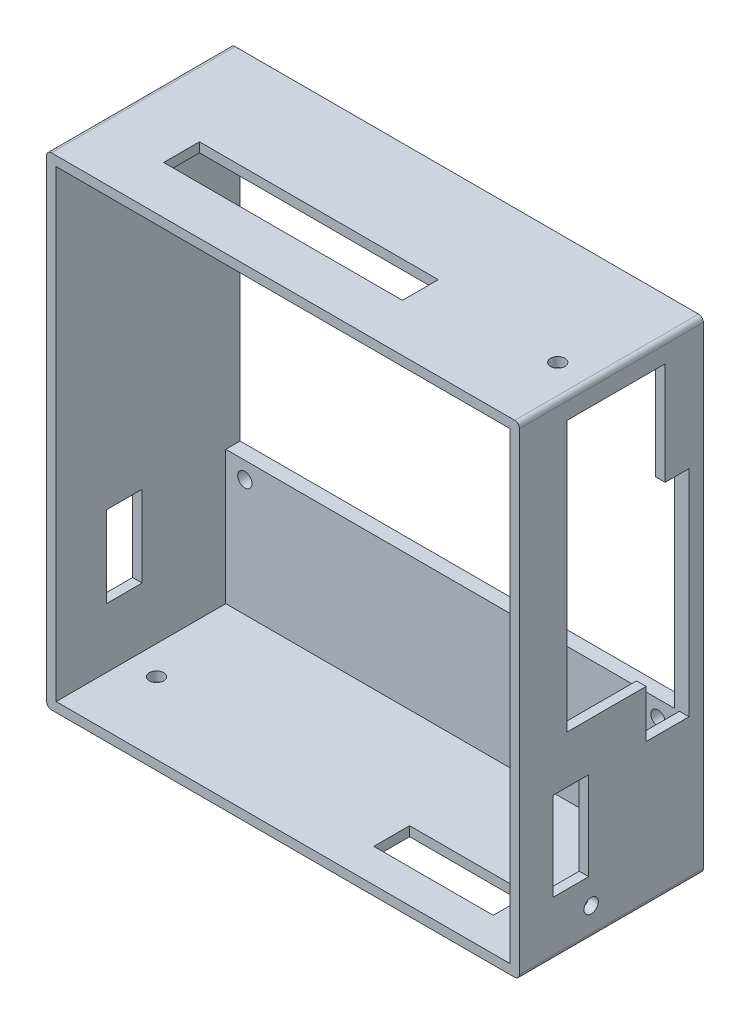
SolidWorks part; units mm, degrees
ref_plane "前视基准面" through (0, 0, 0) normal (0, 0, 1) x (1, 0, 0)
ref_plane "上视基准面" through (0, 0, 0) normal (0, 1, 0) x (1, 0, 0)
ref_plane "右视基准面" through (0, 0, 0) normal (1, 0, 0) x (0, 0, -1)
sketch "草图1" plane through (0, 0, 0) normal (0, 0, 1) x (1, 0, 0)
  line L1 (-47.5, -30.5) -> (47.5, -30.5)
  line L2 (-47.5, -30.5) -> (-47.5, 30.5)
  line L3 (-47.5, 30.5) -> (47.5, 30.5)
  line L4 (47.5, -30.5) -> (47.5, 30.5)
  line L5 (-47.5, -30.5) -> (47.5, 30.5) construction
  line L6 (-47.5, 30.5) -> (47.5, -30.5) construction
  line L10 (-49.5, 40.5) -> (49.5, 40.5)
  line L11 (49.5, 40.5) -> (49.5, -63.5)
  line L12 (49.5, -63.5) -> (-49.5, -63.5)
  line L13 (-49.5, -63.5) -> (-49.5, 40.5)
  circle A0 centre (43, 34) radius 1.5
  circle A1 centre (-43.5, 34) radius 1.5
  circle A2 centre (-43.5, -34) radius 1.5
  circle A3 centre (43, -34) radius 1.5
  point P0 (0, 0)
extrude "凸台-拉伸3" add sketch "草图1" along normal blind 3
sketch "草图3" plane through (0, 0, 3) normal (0, 0, 1) x (1, 0, 0)
  line L0 (-47.5, 38.5) -> (-47.5, -61.5)
  line L1 (-47.5, -61.5) -> (47.5, -61.5)
  line L2 (47.5, -61.5) -> (47.5, 38.5)
  line L3 (47.5, 38.5) -> (-47.5, 38.5)
  line L4 (-49.5, 40.5) -> (-49.5, -63.5)
  line L5 (-49.5, -63.5) -> (49.5, -63.5)
  line L6 (49.5, -63.5) -> (49.5, 40.5)
  line L7 (49.5, 40.5) -> (-49.5, 40.5)
  line L8 (-49.5, 40.5) -> (-49.5, -63.5)
  line L9 (-49.5, -63.5) -> (49.5, -63.5)
  line L10 (49.5, -63.5) -> (49.5, 40.5)
  line L11 (49.5, 40.5) -> (-49.5, 40.5)
  dimension "D1" = 0
  dimension "D2" = 2
extrude "凸台-拉伸4" add sketch "草图3" along normal blind 33
sketch "草图4" plane through (47.5, 0, 0) normal (-1, 0, 0) x (0, 0, 1)
  line L2 (12, 14.5) -> (12, -30.5)
  line L3 (12, -30.5) -> (3, -30.5)
  line L5 (0, 14.5) -> (0, -30.5)
  line L6 (0, -30.5) -> (3, -30.5)
  line L7 (12, 14.5) -> (0, 14.5)
extrude "切除-拉伸2" cut sketch "草图4" against normal blind 30
sketch "草图5" plane through (0, 40.5, 0) normal (0, 1, 0) x (1, 0, 0)
  line L0 (15, -28.5) -> (-35, -28.5)
  line L2 (-35, -21) -> (15, -21)
  line L3 (-35, -28.5) -> (-35, -21)
  line L4 (15, -21) -> (15, -28.5)
extrude "切除-拉伸3" cut sketch "草图5" against normal blind 30
sketch "草图6" plane through (47.5, 0, 0) normal (-1, 0, 0) x (0, 0, 1)
  line L0 (36, 38.5) -> (36, -16.5)
  line L1 (36, -61.5) -> (36, 38.5) construction
  line L2 (36, 38.5) -> (3, 38.5) construction
  line L3 (36, -16.5) -> (8, -16.5)
  line L4 (8, -16.5) -> (8, 38.5)
  line L5 (8, 38.5) -> (36, 38.5)
extrude "切除-拉伸4" cut sketch "草图6" against normal blind 30
sketch "草图7" plane through (47.5, 0, 0) normal (-1, 0, 0) x (0, 0, 1)
  line L1 (24, -30.5) -> (24, -49)
  line L5 (24, -30.5) -> (31.5, -30.5)
  line L6 (31.5, -30.5) -> (31.5, -49)
  line L7 (31.5, -49) -> (24, -49)
extrude "切除-拉伸5" cut sketch "草图7" against normal blind 30
sketch "草图8" plane through (0, -61.5, 0) normal (0, 1, 0) x (1, 0, 0)
  line L2 (40, -28.5) -> (15, -28.5)
  line L3 (15, -28.5) -> (15, -21)
  line L4 (15, -21) -> (40, -21)
  line L5 (40, -21) -> (40, -28.5)
extrude "切除-拉伸6" cut sketch "草图8" against normal blind 30
fillet "圆角1" radius 1 4 edges at (-49.5, 40.5, 18) (49.5, 40.5, 18) (49.5, -63.5, 18) (-49.5, -63.5, 18)
sketch "草图9" plane through (0, 0, 36) normal (0, 0, 1) x (1, 0, 0)
  line L0 (47.5, -16.5) -> (47.5, 38.5)
  line L1 (49.5, 38.5) -> (-47.5, 38.5) construction
  line L2 (47.5, 38.5) -> (49.5, 38.5)
  line L3 (49.5, 38.5) -> (49.5, -16.5)
  line L4 (49.5, -16.5) -> (47.5, -16.5)
extrude "凸台-拉伸5" add sketch "草图9" against normal blind 7.5
sketch "草图14" plane through (0, -61.5, 0) normal (0, 1, 0) x (1, 0, 0)
  line L0 (40, -28.5) -> (40, -21) construction
  line L1 (40, -21) -> (15, -21) construction
  line L2 (15, -28.5) -> (40, -28.5) construction
  line L3 (15, -21) -> (15, -28.5) construction
  line L4 (47.5, -3) -> (-47.5, -3)
  line L5 (-47.5, -3) -> (-47.5, -36)
  line L6 (-47.5, -36) -> (47.5, -36)
  line L7 (47.5, -36) -> (47.5, -3)
  line L8 (47.5, -3) -> (-47.5, -3)
  line L9 (-47.5, -3) -> (-47.5, -36)
  line L10 (-47.5, -36) -> (47.5, -36)
  line L11 (47.5, -36) -> (47.5, -3)
  line L12 (40, -28.5) -> (40, -21)
  line L13 (40, -21) -> (15, -21)
  line L14 (15, -28.5) -> (40, -28.5)
  line L15 (15, -21) -> (15, -28.5)
  dimension "D1" = 0
extrude "凸台-拉伸6" add sketch "草图14" along normal blind 3
sketch "草图15" plane through (0, -63.5, 0) normal (0, -1, 0) x (1, 0, 0)
  line L1 (92.1466, -51.2955) -> (-86.0456, -51.2955)
  line L2 (92.1466, -51.2955) -> (92.1466, 83.0993)
  line L3 (92.1466, 83.0993) -> (-86.0456, 83.0993)
  line L4 (-86.0456, -51.2955) -> (-86.0456, 83.0993)
  line L5 (92.1466, -51.2955) -> (-86.0456, 83.0993) construction
  line L6 (92.1466, 83.0993) -> (-86.0456, -51.2955) construction
  point P0 (3.0505, 15.9019)
extrude "切除-拉伸8" cut sketch "草图15" against normal blind 3
sketch "草图16" plane through (0, 0, 0) normal (0, 0, -1) x (-1, 0, 0)
  line L1 (-47.5, 30.5) -> (-46.5, 30.5)
  line L2 (-47.5, 30.5) -> (47.5, 30.5) construction
  line L3 (-46.5, 30.5) -> (-46.5, -30.5)
  line L4 (47.5, -30.5) -> (-49.5, -30.5) construction
  line L5 (-46.5, -30.5) -> (-49.5, -30.5)
  line L6 (-49.5, -30.5) -> (-49.5, 14.5)
  line L7 (-47.5, 30.5) -> (-47.5, 14.5)
  line L8 (-47.5, 14.5) -> (-49.5, 14.5)
extrude "凸台-拉伸7" add sketch "草图16" against normal blind 3
sketch "草图17" plane through (-49.5, 0, 0) normal (-1, 0, 0) x (0, 0, 1)
  line L11 (28, -46) -> (28, -29)
  line L17 (20.5, -46) -> (28, -46)
  line L18 (20.5, -46) -> (20.5, -29)
  line L19 (20.5, -29) -> (28, -29)
extrude "切除-拉伸9" cut sketch "草图17" against normal blind 3
fillet "圆角3" radius 1 2 edges at (-49.5, -60.5, 18) (49.5, -60.5, 18)
sketch "草图19" plane through (0, 0, 36) normal (0, 0, 1) x (1, 0, 0)
  line L4 (47.5, -58.5) -> (47.5, 38.5)
  line L5 (-47.5, -58.5) -> (47.5, -58.5)
  line L6 (-47.5, 38.5) -> (-47.5, -58.5)
  line L7 (47.5, 38.5) -> (-47.5, 38.5)
  line L8 (47.5, -58.5) -> (47.5, 38.5)
  line L9 (-47.5, -58.5) -> (47.5, -58.5)
  line L10 (-47.5, 38.5) -> (-47.5, -58.5)
  line L11 (47.5, 38.5) -> (-47.5, 38.5)
  line L12 (-49.5, 39.5) -> (-49.5, -59.5)
  line L13 (-48.5, -60.5) -> (48.5, -60.5)
  line L14 (49.5, -59.5) -> (49.5, 39.5)
  line L15 (48.5, 40.5) -> (-48.5, 40.5)
  line L16 (-49.5, 39.5) -> (-49.5, -59.5)
  line L17 (-48.5, -60.5) -> (48.5, -60.5)
  line L18 (49.5, -59.5) -> (49.5, 39.5)
  line L19 (48.5, 40.5) -> (-48.5, 40.5)
  arc A4 (-49.5, -59.5) -> (-48.5, -60.5) centre (-48.5, -59.5) ccw
  arc A5 (48.5, -60.5) -> (49.5, -59.5) centre (48.5, -59.5) ccw
  arc A6 (49.5, 39.5) -> (48.5, 40.5) centre (48.5, 39.5) ccw
  arc A7 (-48.5, 40.5) -> (-49.5, 39.5) centre (-48.5, 39.5) ccw
  arc A8 (-49.5, -59.5) -> (-48.5, -60.5) centre (-48.5, -59.5) ccw
  arc A9 (48.5, -60.5) -> (49.5, -59.5) centre (48.5, -59.5) ccw
  arc A10 (49.5, 39.5) -> (48.5, 40.5) centre (48.5, 39.5) ccw
  arc A11 (-48.5, 40.5) -> (-49.5, 39.5) centre (-48.5, 39.5) ccw
  dimension "D1" = 0
  dimension "D2" = 0
extrude "凸台-拉伸8" add sketch "草图19" along normal blind 2.5
sketch "草图20" plane through (0, 38.5, 0) normal (0, -1, 0) x (1, 0, 0)
  line L1 (47.5, 8) -> (49.5, 8)
  line L2 (47.5, 8) -> (47.5, 28.5)
  line L3 (47.5, 28.5) -> (49.5, 28.5)
  line L4 (49.5, 8) -> (49.5, 28.5)
extrude "凸台-拉伸9" add sketch "草图20" along normal blind 2.5
sketch "草图21" plane through (0, -60.5, 0) normal (0, -1, 0) x (1, 0, 0)
  line L0 (15, 21) -> (15, 28.5) construction
  line L4 (15, 21) -> (15, 28.5)
  line L10 (43, 31.5) -> (18, 31.5)
  line L12 (43, 31.5) -> (43, 24)
  line L13 (43, 24) -> (18, 24)
  line L14 (18, 24) -> (18, 31.5)
  line M10 (15, 28.5) -> (40, 28.5)
  line M11 (40, 28.5) -> (40, 21)
extrude "切除-拉伸10" cut sketch "草图21" against normal blind 2 contours L14 L13 L12 L10 M10 M11 region at (32.178, -60.5, 29.428)
sketch "草图23" plane through (0, -60.5, 0) normal (0, -1, 0) x (1, 0, 0)
  line L0 (15, 28.5) -> (18, 28.5) construction
  line L1 (15, 21) -> (15, 28.5) construction
  line L2 (40, 21) -> (15, 21) construction
  line L3 (40, 24) -> (40, 21) construction
  line L4 (15, 28.5) -> (18, 28.5)
  line L5 (15, 21) -> (15, 28.5)
  line L6 (40, 21) -> (15, 21)
  line L7 (40, 24) -> (40, 21)
  line L8 (40, 24) -> (18, 24)
  line L9 (18, 24) -> (18, 28.5)
extrude "凸台-拉伸11" add sketch "草图23" against normal blind 2
sketch "草图24" plane through (49.5, 0, 0) normal (1, 0, 0) x (0, 0, -1)
  circle A0 centre (-23.5, -54.5) radius 1.5
extrude "切除-拉伸11" cut sketch "草图24" against normal blind 2
sketch "草图25" plane through (0, -60.5, 0) normal (0, -1, 0) x (1, 0, 0)
  circle A1 centre (-41.5, 23.5) radius 1.5
extrude "切除-拉伸12" cut sketch "草图25" against normal blind 2
sketch "草图26" plane through (-49.5, 0, 0) normal (-1, 0, 0) x (0, 0, 1)
  circle A0 centre (23.5, 33.5) radius 1.5
extrude "切除-拉伸13" cut sketch "草图26" against normal blind 2
sketch "草图27" plane through (0, 40.5, 0) normal (0, 1, 0) x (1, 0, 0)
  circle A1 centre (42.5, -23.5) radius 1.5
extrude "切除-拉伸14" cut sketch "草图27" against normal blind 2
sketch "草图28" plane through (0, -16.5, 0) normal (0, 1, 0) x (1, 0, 0)
  line L4 (47.5, -12) -> (47.5, -28.5)
  line L5 (47.5, -28.5) -> (49.5, -28.5)
  line L6 (49.5, -28.5) -> (49.5, -12)
  line L7 (49.5, -12) -> (47.5, -12)
  line L8 (47.5, -12) -> (47.5, -28.5)
  line L9 (47.5, -28.5) -> (49.5, -28.5)
  line L10 (49.5, -28.5) -> (49.5, -12)
  line L11 (49.5, -12) -> (47.5, -12)
  dimension "D1" = 0
extrude "切除-拉伸15" cut sketch "草图28" against normal blind 4
sketch "草图29" plane through (0, -60.5, 0) normal (0, -1, 0) x (1, 0, 0)
  line L0 (43, 24) -> (37, 24)
  line L1 (43, 24) -> (18, 24) construction
  line L2 (37, 24) -> (37, 31.5)
  line L3 (43, 31.5) -> (18, 31.5) construction
  line L4 (37, 31.5) -> (43, 31.5)
  line L5 (43, 31.5) -> (43, 24)
extrude "凸台-拉伸12" add sketch "草图29" against normal blind 2
sketch "草图30" plane through (0, -60.5, 0) normal (0, -1, 0) x (1, 0, 0)
  line L0 (18, 24) -> (12, 24)
  line L1 (18, 24) -> (18, 31.5)
  line L2 (18, 31.5) -> (12, 31.5)
  line L3 (12, 31.5) -> (12, 24)
extrude "切除-拉伸16" cut sketch "草图30" against normal blind 2
